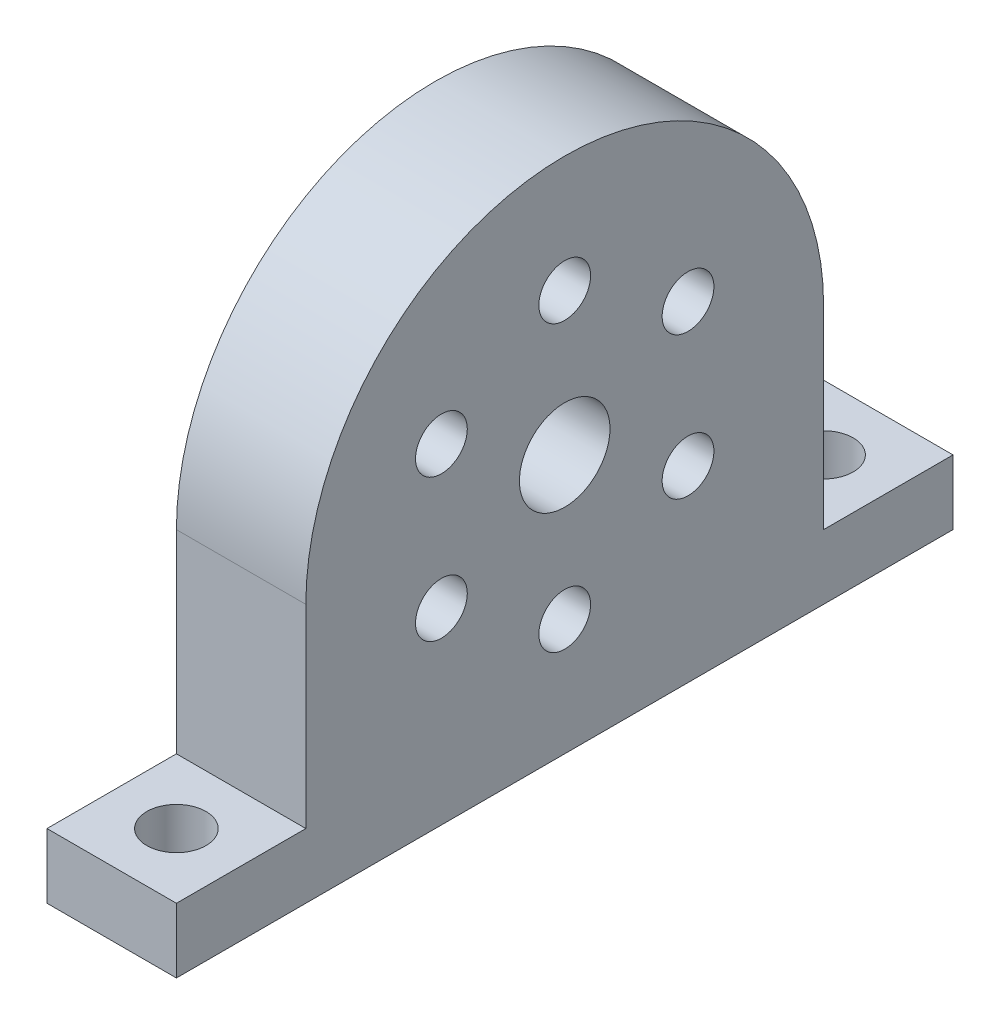
SolidWorks part; units mm, degrees
ref_plane "Front Plane" through (0, 0, 0) normal (0, 0, 1) x (1, 0, 0)
ref_plane "Top Plane" through (0, 0, 0) normal (0, 1, 0) x (1, 0, 0)
ref_plane "Right Plane" through (0, 0, 0) normal (1, 0, 0) x (0, 0, -1)
sketch "Sketch1" plane through (0, 0, 0) normal (1, 0, 0) x (0, 0, -1)
  line L0 (20, -15) -> (30, -15)
  line L1 (-30, -20) -> (30, -20)
  line L2 (-30, -20) -> (-30, -15)
  line L3 (-30, -15) -> (-20, -15)
  line L4 (30, -20) -> (30, -15)
  line L6 (-20, 0) -> (-20, -15)
  line L7 (-22.3599, -20) -> (-15.8566, -20)
  line L10 (20, 0) -> (20, -15)
  line L11 (17.6401, -20) -> (9.951, -20)
  circle A1 centre (0, 11) radius 2
  circle A2 centre (9.5263, 5.5) radius 2
  circle A3 centre (9.5263, -5.5) radius 2
  circle A4 centre (0, -11) radius 2
  circle A5 centre (-9.5263, -5.5) radius 2
  circle A6 centre (-9.5263, 5.5) radius 2
  arc A7 (20, 0) -> (-20, 0) centre (0, 0) ccw
  circle A8 centre (0, 0) radius 3.5
  point P18 (0, 0)
  dimension "D1" = 4
  dimension "D2" = 7
  dimension "D5" = 20
  dimension "D11" = 9.951
  dimension "D3" = 11
  dimension "D6" = 30
  dimension "D7" = 30
  dimension "D8" = 5
  dimension "D9" = 10
  dimension "D10" = 20
  dimension "D12" = 17.6401
  dimension "D13" = 15.8566
  dimension "D14" = 22.3599
  dimension "D4" = 6
extrude "Boss-Extrude1" add sketch "Sketch1" along normal blind 10 contours L10 A7 L6 L3 L2 L1 L4 L0 A8 A1 A2 A3 A4 A5 A6 region at (0, -15.7211, -25)
hole_wizard "#8 (0.18) Diameter Hole1" positions "3DSketch1" profile "Sketch2" hole size "#8" standard "ANSI Inch"
sketch3d "3DSketch1"
  line L0 (0, -15, -20) -> (0, -15, -30) construction
  line L1 (10, -15, -30) -> (0, -15, -30) construction
  line L2 (10, -15, 30) -> (0, -15, 30) construction
  line L3 (0, -15, 30) -> (0, -15, 20) construction
  point P0 (5, -15, -25)
  point P2 (5, -15, 25)
  dimension "D1" = 5
  dimension "D2" = 5
  dimension "D3" = 5
  dimension "D4" = 5
sketch "Sketch2" plane through (5, -15, -25) normal (1, 0, 0) x (0, 0, 1)
  line L0 (0, 0) -> (0, 5)
  line L1 (0, 5) -> (2.286, 5)
  line L2 (2.286, 5) -> (2.286, 0)
  line L5 (2.286, 0) -> (0, 0)
  line L10 (0, 5) -> (-2.286, 5) construction
  line L11 (0, -6.35) -> (0, 107.95) construction
  dimension "Hole Dia." = 4.572
  dimension "Hole Depth" = 5
  dimension "Drill Angle" = 180
hole_wizard "CSK for M2 Flat Head Machine Screw1" positions "Sketch3" profile "Sketch4" countersink size "M2" standard "ANSI Metric" end condition through all
sketch "Sketch3" plane through (0, 0, 0) normal (-1, 0, 0) x (0, 0, 1)
  point P0 (0, 11)
  point P3 (9.5263, 5.5)
  point P6 (9.5263, -5.5)
  point P9 (0, -11)
  point P12 (-9.5263, -5.5)
  point P15 (-9.5263, 5.5)
sketch "Sketch4" plane through (0, 11, 0) normal (0, 1, 0) x (0, 0, 1)
  line L0 (0, 0) -> (0, 10)
  line L1 (0, 10) -> (1.5, 10)
  line L2 (1.5, 10) -> (1.5, 1.3)
  line L3 (1.5, 1.3) -> (2.8, 0)
  line L5 (2.8, 0) -> (0, 0)
  line L6 (-1.5, 1.3) -> (-2.8, 0) construction
  line L11 (0, -6.35) -> (0, 107.95) construction
  dimension "Thru Hole Dia." = 3
  dimension "Thru Hole Depth" = 10
  dimension "Near C'Sink Dia." = 5.6
  dimension "Near C'Sink Angle" = 90
